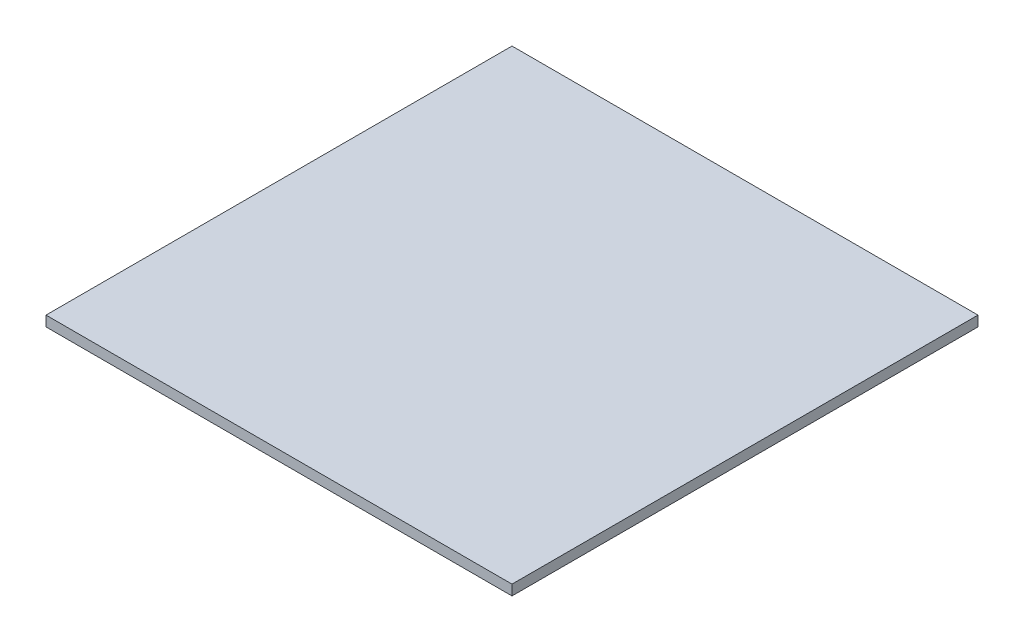
SolidWorks part; units mm, degrees
ref_plane "Front Plane" through (0, 0, 0) normal (0, 0, 1) x (1, 0, 0)
ref_plane "Top Plane" through (0, 0, 0) normal (0, 1, 0) x (1, 0, 0)
ref_plane "Right Plane" through (0, 0, 0) normal (1, 0, 0) x (0, 0, -1)
sketch "Sketch1" plane through (0, 0, 0) normal (0, 1, 0) x (1, 0, 0)
  line L1 (-144.4625, 144.4625) -> (144.4625, 144.4625)
  line L2 (-144.4625, 144.4625) -> (-144.4625, -144.4625)
  line L3 (-144.4625, -144.4625) -> (144.4625, -144.4625)
  line L4 (144.4625, 144.4625) -> (144.4625, -144.4625)
  point P4 (0, 144.4625)
  point P6 (-144.4625, 0)
  dimension "D1" = 288.925
extrude "Boss-Extrude1" add sketch "Sketch1" along normal blind 6.3596 contours L2 L1 L4 L3
